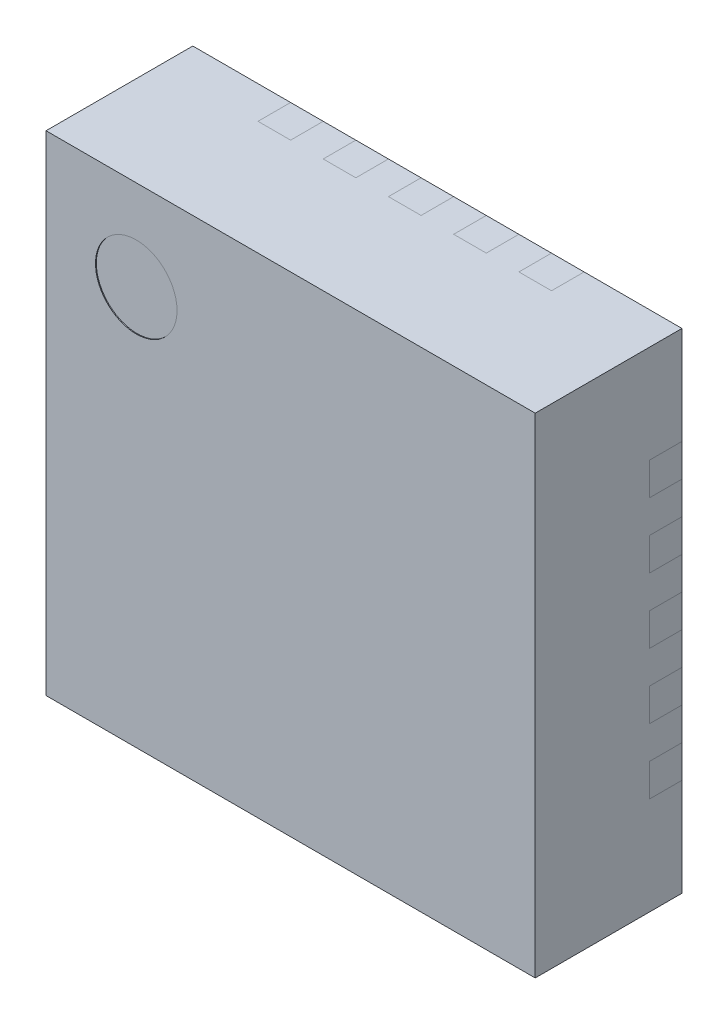
SolidWorks part; units mm, degrees
ref_plane "Front Plane" through (0, 0, 0) normal (0, 0, 1) x (1, 0, 0)
ref_plane "Top Plane" through (0, 0, 0) normal (0, 1, 0) x (1, 0, 0)
ref_plane "Right Plane" through (0, 0, 0) normal (1, 0, 0) x (0, 0, -1)
sketch "Sketch1" plane through (0, 0, 0) normal (0, 0, 1) x (1, 0, 0)
  line L1 (1.5, 1.5) -> (-1.5, 1.5)
  line L2 (1.5, 1.5) -> (1.5, -1.5)
  line L3 (1.5, -1.5) -> (-1.5, -1.5)
  line L4 (-1.5, 1.5) -> (-1.5, -1.5)
  line L5 (1.5, 1.5) -> (-1.5, -1.5) construction
  line L6 (1.5, -1.5) -> (-1.5, 1.5) construction
  point P0 (0, 0)
  dimension "D1" = 3
extrude "Boss-Extrude1" add sketch "Sketch1" along normal blind 0.9
sketch "Sketch2" plane through (1.5, 0, 0) normal (1, 0, 0) x (0, 0, -1)
  line L0 (-0.2, -0.5) -> (-0.2, -0.3)
  line L1 (-0.2, -0.1) -> (0.2, -0.1)
  line L2 (-0.2, -0.1) -> (-0.2, 0.1)
  line L3 (-0.2, 0.1) -> (0.2, 0.1)
  line L4 (0.2, -0.1) -> (0.2, 0.1)
  line L5 (-0.2, -0.1) -> (0.2, 0.1) construction
  line L6 (-0.2, 0.1) -> (0.2, -0.1) construction
  line L7 (0, -1.5) -> (0, 1.5) construction
  line L8 (-0.2, -0.3) -> (0.2, -0.3)
  line L9 (0.2, -0.5) -> (0.2, -0.3)
  line L10 (-0.2, -0.5) -> (0.2, -0.5)
  line L11 (-0.2, -0.9) -> (-0.2, -0.7)
  line L12 (-0.2, -0.7) -> (0.2, -0.7)
  line L13 (0.2, -0.9) -> (0.2, -0.7)
  line L14 (-0.2, -0.9) -> (0.2, -0.9)
  line L15 (-0.2, -0.1) -> (-0.2, 0.1)
  line L16 (-0.2, 0.1) -> (0.2, 0.1)
  line L17 (0.2, -0.1) -> (0.2, 0.1)
  line L18 (-0.2, -0.1) -> (0.2, -0.1)
  line L19 (-0.2, -0.5) -> (-0.2, -0.3)
  line L20 (-0.2, -0.3) -> (0.2, -0.3)
  line L21 (0.2, -0.5) -> (0.2, -0.3)
  line L22 (-0.2, -0.5) -> (0.2, -0.5)
  line L23 (-0.2, 0.3) -> (-0.2, 0.5)
  line L24 (-0.2, 0.5) -> (0.2, 0.5)
  line L25 (0.2, 0.3) -> (0.2, 0.5)
  line L26 (-0.2, 0.3) -> (0.2, 0.3)
  line L27 (-0.2, -0.1) -> (-0.2, 0.1)
  line L28 (-0.2, 0.1) -> (0.2, 0.1)
  line L29 (0.2, -0.1) -> (0.2, 0.1)
  line L30 (-0.2, -0.1) -> (0.2, -0.1)
  line L31 (-0.2, 0.3) -> (-0.2, 0.5)
  line L32 (-0.2, 0.5) -> (0.2, 0.5)
  line L33 (0.2, 0.3) -> (0.2, 0.5)
  line L34 (-0.2, 0.3) -> (0.2, 0.3)
  line L35 (-0.2, 0.7) -> (-0.2, 0.9)
  line L36 (-0.2, 0.9) -> (0.2, 0.9)
  line L37 (0.2, 0.7) -> (0.2, 0.9)
  line L38 (-0.2, 0.7) -> (0.2, 0.7)
  point P0 (0, 0)
  line M3 (0, -1.5) -> (0, 1.5)
  dimension "D1" = 0.2
  dimension "D2" = 0.2
  dimension "D3" = 3
  dimension "D4" = 3
extrude "Cut-Extrude1" cut sketch "Sketch2" against normal blind 0.5 contours L11 L14 L12 M3 | L0 L10 L8 M3 | L3 L2 L1 M3 | L23 L26 L24 M3 | L35 L38 L36 M3 | L38 L37 L36 M3 | L26 L25 L24 M3 | L1 L4 L3 M3 | L10 L9 L8 M3 | L14 L13 L12 M3 region at (1.5, 0.8, 0.1) region at (1.5, 0.8, -0.1) region at (1.5, 0.4, 0.1) region at (1.5, 0.4, -0.1) region at (1.5, 0, 0.1) region at (1.5, 0, -0.1) region at (1.5, -0.8, -0.1) region at (1.5, -0.8, 0.1) region at (1.5, -0.4, 0.1) region at (1.5, -0.4, -0.1)
ref_plane "Plane1" through (0, 0, 0) normal (0, -1, 0) x (-1, 0, 0)
ref_plane "Plane2" through (0, 0, 0) normal (1, 0, 0) x (0, 0, -1)
ref_axis "Axis1" through (0, 0, -0.045) along (0, 0, 1)
pattern_circular "CirPattern1" count 4 every 90 about axis through (0, 0, -0.045) along (0, 0, 1) of "Cut-Extrude1"
sketch "Sketch4" plane through (0, 0, 0.9) normal (0, 0, 1) x (1, 0, 0)
  line L1 (-1.5, 1.5) -> (-0.9466, 1.5) construction
  line L2 (-1.5, 1.5) -> (-1.5, 0.9466) construction
  line L3 (-1.5, 0.9466) -> (-0.9466, 0.9466) construction
  line L4 (-0.9466, 1.5) -> (-0.9466, 0.9466) construction
  circle A0 centre (-0.9466, 0.9466) radius 0.25
  point P6 (-0.9466, 0.9466)
  dimension "D1" = 0.5
extrude "Cut-Extrude2" cut sketch "Sketch4" against normal blind 0.005
sketch "Sketch5" plane through (0, 0, 0.2) normal (0, 0, -1) x (-1, 0, 0)
  line L0 (-1.5, 0.9) -> (-1.5, 0.7) construction
  line L1 (-1.5, 0.7) -> (-1, 0.7) construction
  line L2 (-1, 0.7) -> (-1, 0.9) construction
  line L3 (-1, 0.9) -> (-1.5, 0.9) construction
  line L4 (-1.5, 0.5) -> (-1.5, 0.3) construction
  line L5 (-1.5, 0.3) -> (-1, 0.3) construction
  line L6 (-1, 0.3) -> (-1, 0.5) construction
  line L7 (-1, 0.5) -> (-1.5, 0.5) construction
  line L8 (-1.5, 0.1) -> (-1.5, -0.1) construction
  line L9 (-1.5, -0.1) -> (-1, -0.1) construction
  line L10 (-1, -0.1) -> (-1, 0.1) construction
  line L11 (-1, 0.1) -> (-1.5, 0.1) construction
  line L12 (-1.5, -0.3) -> (-1.5, -0.5) construction
  line L13 (-1.5, -0.5) -> (-1, -0.5) construction
  line L14 (-1, -0.5) -> (-1, -0.3) construction
  line L15 (-1, -0.3) -> (-1.5, -0.3) construction
  line L16 (-1.5, -0.7) -> (-1.5, -0.9) construction
  line L17 (-1.5, -0.9) -> (-1, -0.9) construction
  line L18 (-1, -0.9) -> (-1, -0.7) construction
  line L19 (-1, -0.7) -> (-1.5, -0.7) construction
  line L20 (-0.9, -1.5) -> (-0.7, -1.5) construction
  line L21 (-0.7, -1.5) -> (-0.7, -1) construction
  line L22 (-0.7, -1) -> (-0.9, -1) construction
  line L23 (-0.9, -1) -> (-0.9, -1.5) construction
  line L24 (-0.5, -1.5) -> (-0.3, -1.5) construction
  line L25 (-0.3, -1.5) -> (-0.3, -1) construction
  line L26 (-0.3, -1) -> (-0.5, -1) construction
  line L27 (-0.5, -1) -> (-0.5, -1.5) construction
  line L28 (-0.1, -1.5) -> (0.1, -1.5) construction
  line L29 (0.1, -1.5) -> (0.1, -1) construction
  line L30 (0.1, -1) -> (-0.1, -1) construction
  line L31 (-0.1, -1) -> (-0.1, -1.5) construction
  line L32 (0.3, -1.5) -> (0.5, -1.5) construction
  line L33 (0.5, -1.5) -> (0.5, -1) construction
  line L34 (0.5, -1) -> (0.3, -1) construction
  line L35 (0.3, -1) -> (0.3, -1.5) construction
  line L36 (0.7, -1.5) -> (0.9, -1.5) construction
  line L37 (0.9, -1.5) -> (0.9, -1) construction
  line L38 (0.9, -1) -> (0.7, -1) construction
  line L39 (0.7, -1) -> (0.7, -1.5) construction
  line L40 (1.5, -0.9) -> (1.5, -0.7) construction
  line L41 (1.5, -0.7) -> (1, -0.7) construction
  line L42 (1, -0.7) -> (1, -0.9) construction
  line L43 (1, -0.9) -> (1.5, -0.9) construction
  line L44 (1.5, -0.5) -> (1.5, -0.3) construction
  line L45 (1.5, -0.3) -> (1, -0.3) construction
  line L46 (1, -0.3) -> (1, -0.5) construction
  line L47 (1, -0.5) -> (1.5, -0.5) construction
  line L48 (1.5, -0.1) -> (1.5, 0.1) construction
  line L49 (1.5, 0.1) -> (1, 0.1) construction
  line L50 (1, 0.1) -> (1, -0.1) construction
  line L51 (1, -0.1) -> (1.5, -0.1) construction
  line L52 (1.5, 0.3) -> (1.5, 0.5) construction
  line L53 (1.5, 0.5) -> (1, 0.5) construction
  line L54 (1, 0.5) -> (1, 0.3) construction
  line L55 (1, 0.3) -> (1.5, 0.3) construction
  line L56 (1.5, 0.7) -> (1.5, 0.9) construction
  line L57 (1.5, 0.9) -> (1, 0.9) construction
  line L58 (1, 0.9) -> (1, 0.7) construction
  line L59 (1, 0.7) -> (1.5, 0.7) construction
  line L60 (0.9, 1.5) -> (0.7, 1.5) construction
  line L61 (0.7, 1.5) -> (0.7, 1) construction
  line L62 (0.7, 1) -> (0.9, 1) construction
  line L63 (0.9, 1) -> (0.9, 1.5) construction
  line L64 (0.5, 1.5) -> (0.3, 1.5) construction
  line L65 (0.3, 1.5) -> (0.3, 1) construction
  line L66 (0.3, 1) -> (0.5, 1) construction
  line L67 (0.5, 1) -> (0.5, 1.5) construction
  line L68 (0.1, 1.5) -> (-0.1, 1.5) construction
  line L69 (-0.1, 1.5) -> (-0.1, 1) construction
  line L70 (-0.1, 1) -> (0.1, 1) construction
  line L71 (0.1, 1) -> (0.1, 1.5) construction
  line L72 (-0.3, 1.5) -> (-0.5, 1.5) construction
  line L73 (-0.5, 1.5) -> (-0.5, 1) construction
  line L74 (-0.5, 1) -> (-0.3, 1) construction
  line L75 (-0.3, 1) -> (-0.3, 1.5) construction
  line L76 (-0.7, 1.5) -> (-0.9, 1.5) construction
  line L77 (-0.9, 1.5) -> (-0.9, 1) construction
  line L78 (-0.9, 1) -> (-0.7, 1) construction
  line L79 (-0.7, 1) -> (-0.7, 1.5) construction
  line L80 (-1.5, 0.9) -> (-1.5, 0.7)
  line L81 (-1.5, 0.7) -> (-1, 0.7)
  line L82 (-1, 0.7) -> (-1, 0.9)
  line L83 (-1, 0.9) -> (-1.5, 0.9)
  line L84 (-1.5, 0.5) -> (-1.5, 0.3)
  line L85 (-1.5, 0.3) -> (-1, 0.3)
  line L86 (-1, 0.3) -> (-1, 0.5)
  line L87 (-1, 0.5) -> (-1.5, 0.5)
  line L88 (-1.5, 0.1) -> (-1.5, -0.1)
  line L89 (-1.5, -0.1) -> (-1, -0.1)
  line L90 (-1, -0.1) -> (-1, 0.1)
  line L91 (-1, 0.1) -> (-1.5, 0.1)
  line L92 (-1.5, -0.3) -> (-1.5, -0.5)
  line L93 (-1.5, -0.5) -> (-1, -0.5)
  line L94 (-1, -0.5) -> (-1, -0.3)
  line L95 (-1, -0.3) -> (-1.5, -0.3)
  line L96 (-1.5, -0.7) -> (-1.5, -0.9)
  line L97 (-1.5, -0.9) -> (-1, -0.9)
  line L98 (-1, -0.9) -> (-1, -0.7)
  line L99 (-1, -0.7) -> (-1.5, -0.7)
  line L100 (-0.9, -1.5) -> (-0.7, -1.5)
  line L101 (-0.7, -1.5) -> (-0.7, -1)
  line L102 (-0.7, -1) -> (-0.9, -1)
  line L103 (-0.9, -1) -> (-0.9, -1.5)
  line L104 (-0.5, -1.5) -> (-0.3, -1.5)
  line L105 (-0.3, -1.5) -> (-0.3, -1)
  line L106 (-0.3, -1) -> (-0.5, -1)
  line L107 (-0.5, -1) -> (-0.5, -1.5)
  line L108 (-0.1, -1.5) -> (0.1, -1.5)
  line L109 (0.1, -1.5) -> (0.1, -1)
  line L110 (0.1, -1) -> (-0.1, -1)
  line L111 (-0.1, -1) -> (-0.1, -1.5)
  line L112 (0.3, -1.5) -> (0.5, -1.5)
  line L113 (0.5, -1.5) -> (0.5, -1)
  line L114 (0.5, -1) -> (0.3, -1)
  line L115 (0.3, -1) -> (0.3, -1.5)
  line L116 (0.7, -1.5) -> (0.9, -1.5)
  line L117 (0.9, -1.5) -> (0.9, -1)
  line L118 (0.9, -1) -> (0.7, -1)
  line L119 (0.7, -1) -> (0.7, -1.5)
  line L120 (1.5, -0.9) -> (1.5, -0.7)
  line L121 (1.5, -0.7) -> (1, -0.7)
  line L122 (1, -0.7) -> (1, -0.9)
  line L123 (1, -0.9) -> (1.5, -0.9)
  line L124 (1.5, -0.5) -> (1.5, -0.3)
  line L125 (1.5, -0.3) -> (1, -0.3)
  line L126 (1, -0.3) -> (1, -0.5)
  line L127 (1, -0.5) -> (1.5, -0.5)
  line L128 (1.5, -0.1) -> (1.5, 0.1)
  line L129 (1.5, 0.1) -> (1, 0.1)
  line L130 (1, 0.1) -> (1, -0.1)
  line L131 (1, -0.1) -> (1.5, -0.1)
  line L132 (1.5, 0.3) -> (1.5, 0.5)
  line L133 (1.5, 0.5) -> (1, 0.5)
  line L134 (1, 0.5) -> (1, 0.3)
  line L135 (1, 0.3) -> (1.5, 0.3)
  line L136 (1.5, 0.7) -> (1.5, 0.9)
  line L137 (1.5, 0.9) -> (1, 0.9)
  line L138 (1, 0.9) -> (1, 0.7)
  line L139 (1, 0.7) -> (1.5, 0.7)
  line L140 (0.9, 1.5) -> (0.7, 1.5)
  line L141 (0.7, 1.5) -> (0.7, 1)
  line L142 (0.7, 1) -> (0.9, 1)
  line L143 (0.9, 1) -> (0.9, 1.5)
  line L144 (0.5, 1.5) -> (0.3, 1.5)
  line L145 (0.3, 1.5) -> (0.3, 1)
  line L146 (0.3, 1) -> (0.5, 1)
  line L147 (0.5, 1) -> (0.5, 1.5)
  line L148 (0.1, 1.5) -> (-0.1, 1.5)
  line L149 (-0.1, 1.5) -> (-0.1, 1)
  line L150 (-0.1, 1) -> (0.1, 1)
  line L151 (0.1, 1) -> (0.1, 1.5)
  line L152 (-0.3, 1.5) -> (-0.5, 1.5)
  line L153 (-0.5, 1.5) -> (-0.5, 1)
  line L154 (-0.5, 1) -> (-0.3, 1)
  line L155 (-0.3, 1) -> (-0.3, 1.5)
  line L156 (-0.7, 1.5) -> (-0.9, 1.5)
  line L157 (-0.9, 1.5) -> (-0.9, 1)
  line L158 (-0.9, 1) -> (-0.7, 1)
  line L159 (-0.7, 1) -> (-0.7, 1.5)
extrude "Boss-Extrude2" add sketch "Sketch5" along normal up to surface (0.2 mm away) separate body up to face at (0, 0, 0)
